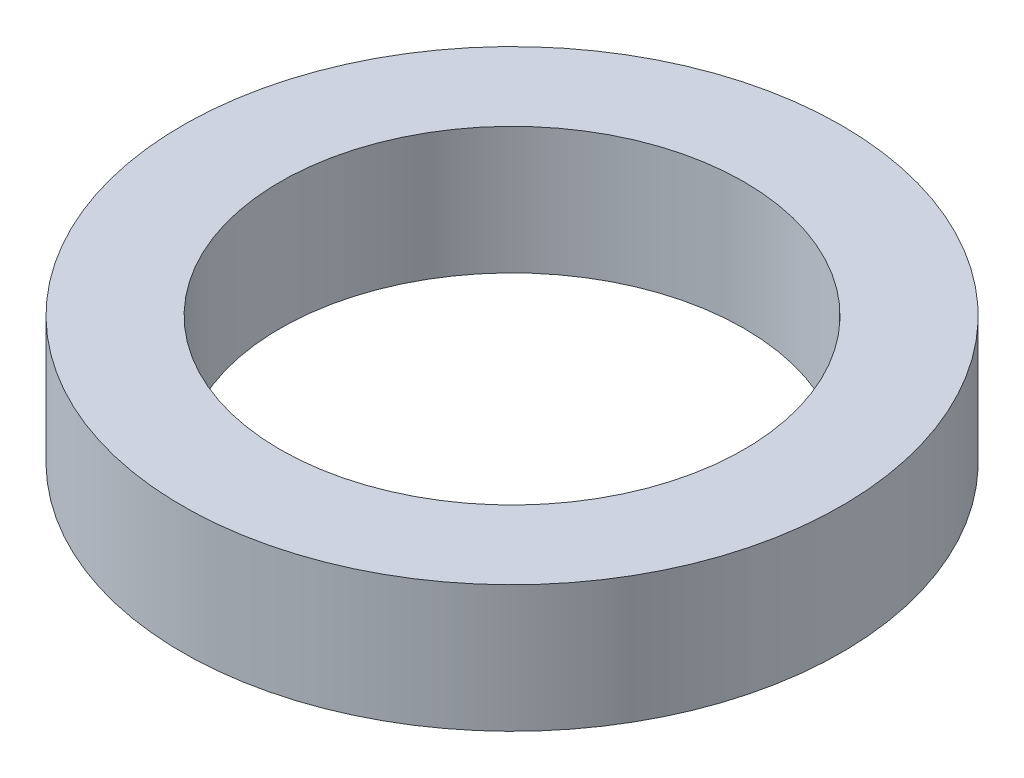
SolidWorks part; units mm, degrees
ref_plane "Front Plane" through (0, 0, 0) normal (0, 0, 1) x (1, 0, 0)
ref_plane "Top Plane" through (0, 0, 0) normal (0, 1, 0) x (1, 0, 0)
ref_plane "Right Plane" through (0, 0, 0) normal (1, 0, 0) x (0, 0, -1)
sketch "Sketch1" plane through (0, 0, 0) normal (0, 1, 0) x (1, 0, 0)
  circle A0 centre (0, 0) radius 67.5
  dimension "FLANGE_OD" = 135
extrude "Boss-Extrude1" add sketch "Sketch1" along normal blind 26
sketch "Sketch2" plane through (0, 0, 0) normal (0, 1, 0) x (1, 0, 0)
  circle A0 centre (0, 0) radius 47.5
  dimension "BORE_D" = 95
extrude "Cut-Extrude1" cut sketch "Sketch2" along normal through all
sketch "Sketch3" plane through (0, 26, 0) normal (0, 1, 0) x (1, 0, 0)
  circle A0 centre (0, 0) radius 25.7919 construction
  circle A1 centre (-25.7919, 0) radius 2.1087
  dimension "BOLT_D" = 4.2174
  dimension "BOLT_PCD" = 51.5839
extrude "Cut-Extrude2" cut sketch "Sketch3" against normal blind 22.9975 rebuild error yes
pattern_circular "CirPattern1" count 8 over 360 rebuild error yes
